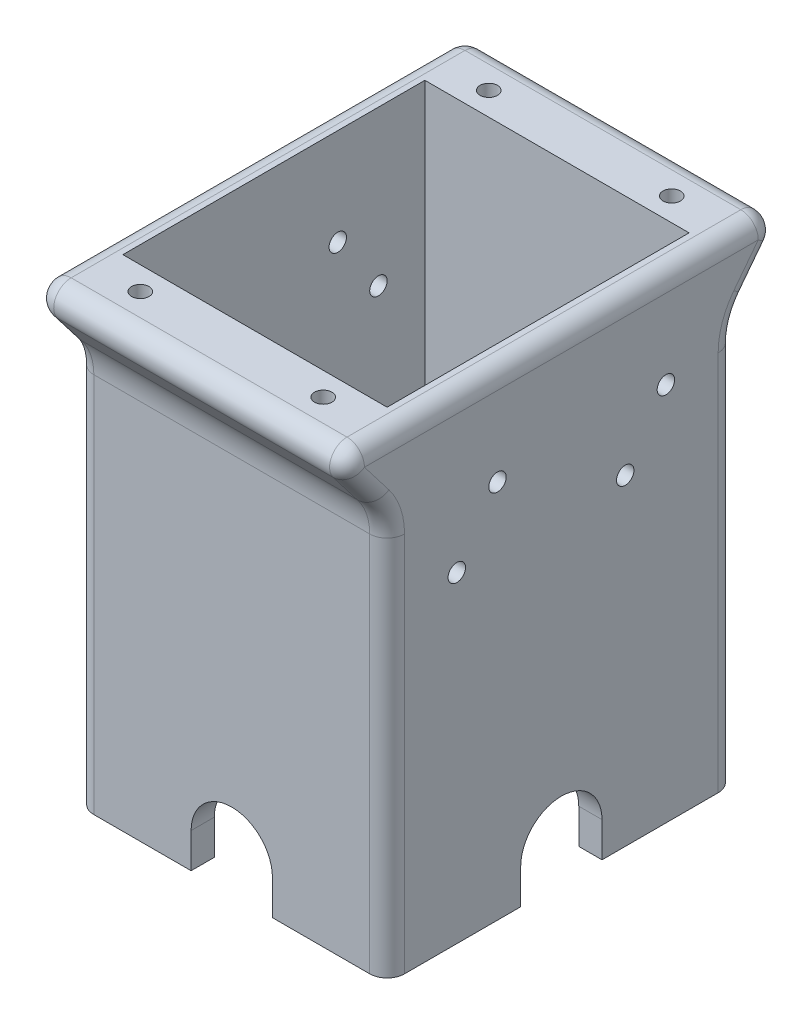
SolidWorks part; units mm, degrees
ref_plane "Front Plane" through (0, 0, 0) normal (0, 0, 1) x (1, 0, 0)
ref_plane "Top Plane" through (0, 0, 0) normal (0, 1, 0) x (1, 0, 0)
ref_plane "Right Plane" through (0, 0, 0) normal (1, 0, 0) x (0, 0, -1)
sketch "Sketch1" plane through (0, 0, 0) normal (0, 1, 0) x (1, 0, 0)
  line L1 (-26.75, 30) -> (26.75, 30)
  line L2 (-26.75, 30) -> (-26.75, -30)
  line L3 (-26.75, -30) -> (26.75, -30)
  line L4 (26.75, 30) -> (26.75, -30)
  line L5 (-26.75, 30) -> (26.75, -30) construction
  line L6 (-26.75, -30) -> (26.75, 30) construction
  line L7 (-22.75, 26) -> (22.75, 26)
  line L8 (-22.75, 26) -> (-22.75, -26)
  line L9 (-22.75, -26) -> (22.75, -26)
  line L10 (22.75, 26) -> (22.75, -26)
  line L11 (-22.75, 26) -> (22.75, -26) construction
  line L12 (-22.75, -26) -> (22.75, 26) construction
  point P0 (0, 0)
  point P6 (0, 0)
  dimension "D1" = 45.5
  dimension "D2" = 4
  dimension "D3" = 4
extrude "Boss-Extrude1" add sketch "Sketch1" along normal blind 82
sketch "Sketch3" plane through (-26.75, 0, 0) normal (-1, 0, 0) x (0, 0, 1)
  line L0 (-30, 82) -> (30, 82) construction
  circle A0 centre (18, 65.35) radius 1.5
  circle A1 centre (11, 55.35) radius 1.5
  dimension "D1" = 3
  dimension "D3" = 3
  dimension "D2" = 16.65
  dimension "D4" = 10
  dimension "D5" = 7
  dimension "D6" = 8
extrude "Cut-Extrude1" cut sketch "Sketch3" against normal blind 4 and the other way through all
pattern_linear "LPattern1" count 2 spacing 29 along (0, 0, -1) of "Cut-Extrude1"
sketch "Sketch4" plane through (26.75, 0, 0) normal (1, 0, 0) x (0, 0, -1)
  line L0 (-30, 82) -> (30, 82) construction
  circle A0 centre (-11, 65.35) radius 1.5
  circle A1 centre (-18, 55.35) radius 1.5
  dimension "D1" = 3
  dimension "D2" = 3
  dimension "D3" = 10
  dimension "D4" = 7
  dimension "D5" = 16.65
  dimension "D6" = 8
extrude "Cut-Extrude2" cut sketch "Sketch4" against normal blind 4
pattern_linear "LPattern2" count 2 spacing 29 along (0, 0, -1) of "Cut-Extrude2"
sketch "Sketch5" plane through (-26.75, 0, 0) normal (-1, 0, 0) x (0, 0, 1)
  line L0 (30, 82) -> (30, 69)
  line L1 (30, 82) -> (30, 0) construction
  line L2 (30, 69) -> (40, 82)
  line L3 (40, 82) -> (30, 82)
  line L4 (-30, 82) -> (-30, 69)
  line L5 (-30, 82) -> (-30, 0) construction
  line L6 (-30, 69) -> (-40, 82)
  line L7 (-30, 82) -> (-40, 82)
  dimension "D1" = 10
  dimension "D2" = 13
extrude "Boss-Extrude2" add sketch "Sketch5" against normal through all
fillet "Fillet1" radius 10 2 edges at (0, 69, 30) (0, 69, -30)
fillet "Fillet2" radius 3 16 edges at (26.75, 32.7994, -30) (26.75, 68.8188, -30.5326) (26.75, 76.8479, -36.0369) (26.75, 82, 0) (0, 82, -40) (26.75, 32.7994, 30) (26.75, 68.8188, 30.5326) (-26.75, 32.7994, 30) (-26.75, 68.8188, 30.5326) (-26.75, 32.7994, -30) (-26.75, 68.8188, -30.5326) (26.75, 76.8479, 36.0369) (0, 82, 40) (-26.75, 76.8479, 36.0369) (-26.75, 76.8479, -36.0369) (-26.75, 82, 0)
sketch "Sketch6" plane through (0, 82, 0) normal (0, 1, 0) x (1, 0, 0)
  line L0 (-22.75, -26) -> (22.75, -26) construction
  line L2 (-23.75, 33.9074) -> (-23.75, -33.9074) construction
  line L3 (0, -33.9074) -> (0, -26) construction
  line L4 (-23.75, -33.9074) -> (23.75, -33.9074) construction
  circle A0 centre (-15.75, -30) radius 1.5
  circle A1 centre (15.75, -30) radius 1.5
  dimension "D2" = 3
  dimension "D1" = 4
  dimension "D3" = 8
extrude "Cut-Extrude3" cut sketch "Sketch6" against normal blind 9
ref_plane "Plane1" through (0, 0, 0) normal (0, 0, 1) x (1, 0, 0)
mirror "Mirror1" about plane through (0, 0, 0) normal (0, 0, 1) of "Cut-Extrude3"
sketch "Sketch7" plane through (26.75, 0, 0) normal (1, 0, 0) x (0, 0, -1)
  line L0 (7, 0) -> (7, 6)
  line L1 (-27, 0) -> (27, 0) construction
  line L2 (-7, 0) -> (-7, 6)
  line L3 (7, 0) -> (-7, 0)
  arc A0 (-7, 6) -> (7, 6) centre (0, 6) cw
  dimension "D5" = 7
  dimension "D1" = 6
  dimension "D2" = 6
  dimension "D3" = 7
  dimension "D4" = 7
extrude "Cut-Extrude4" cut sketch "Sketch7" against normal through all
sketch "Sketch8" plane through (0, 0, -30) normal (0, 0, -1) x (-1, 0, 0)
  line L0 (7, 0) -> (7, 6)
  line L1 (-23.75, 0) -> (23.75, 0) construction
  line L2 (-7, 0) -> (-7, 6)
  line L3 (7, 0) -> (-7, 0)
  arc A0 (-7, 6) -> (7, 6) centre (0, 6) cw
  dimension "D5" = 7
  dimension "D1" = 6
  dimension "D2" = 6
  dimension "D3" = 7
  dimension "D4" = 7
extrude "Cut-Extrude5" cut sketch "Sketch8" against normal through all
